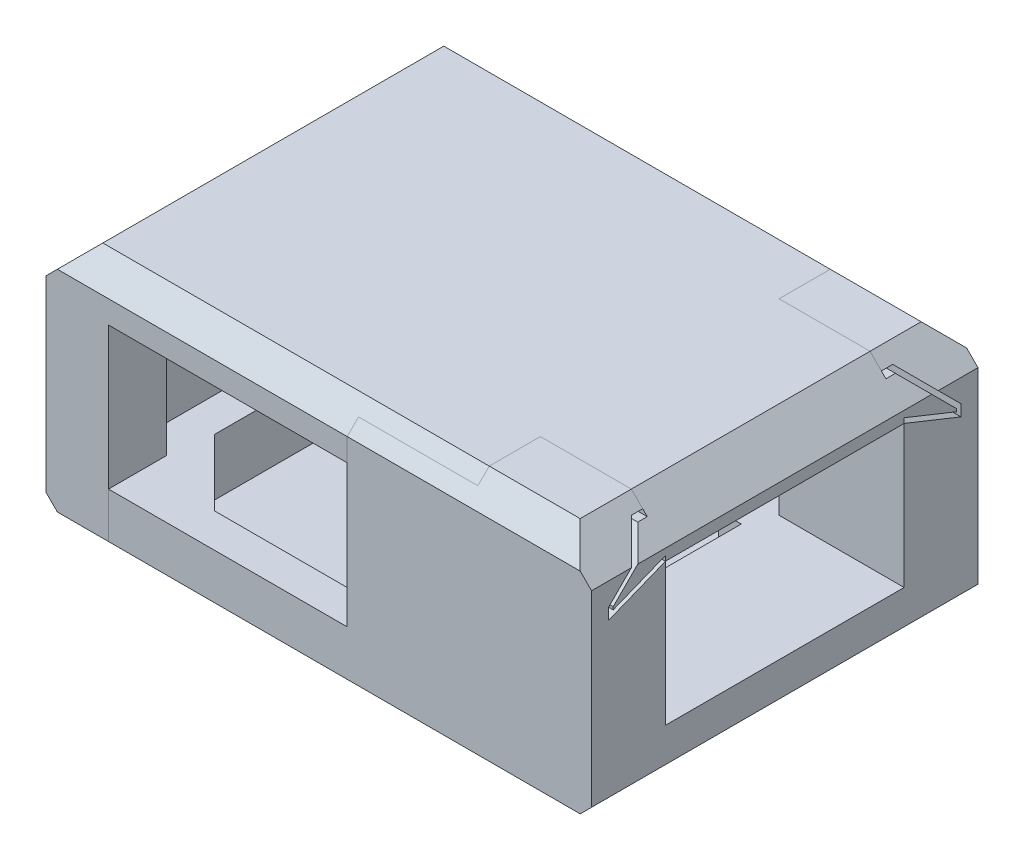
SolidWorks part; units mm, degrees
ref_plane "Front Plane" through (0, 0, 0) normal (0, 0, 1) x (1, 0, 0)
ref_plane "Top Plane" through (0, 0, 0) normal (0, 1, 0) x (1, 0, 0)
ref_plane "Right Plane" through (0, 0, 0) normal (1, 0, 0) x (0, 0, -1)
sketch "Sketch1" plane through (0, 0, 0) normal (0, 1, 0) x (1, 0, 0)
  line L0 (-4.5, 8) -> (-8, 4.5)
  line L1 (8, -8) -> (-4.5, -8)
  line L2 (8, -8) -> (8, 8)
  line L3 (8, 8) -> (-4.5, 8)
  line L4 (-8, -4.5) -> (-8, 4.5)
  line L5 (8, -8) -> (-8, 8) construction
  line L6 (8, 8) -> (-8, -8) construction
  line L7 (-4.5, -8) -> (-8, -4.5)
  point P0 (0, 0)
  dimension "D1" = 16
  dimension "D2" = 16
extrude "Boss-Extrude1" add sketch "Sketch1" along normal blind 1
sketch "Sketch2" plane through (0, 1, 0) normal (0, 1, 0) x (1, 0, 0)
  line L0 (8, -8) -> (8, 8) construction
  line L1 (3, 2) -> (-7, 2)
  line L2 (3, 2) -> (3, 8.5)
  line L3 (3, 8.5) -> (-7, 8.5)
  line L4 (-7, 2) -> (-7, 8.5)
  line L5 (7.5, 5) -> (14, 5)
  line L6 (7.5, 5) -> (7.5, 0)
  line L7 (7.5, 0) -> (14, 0)
  line L8 (14, 5) -> (14, 0)
  line L9 (8, 8) -> (-4.5, 8) construction
  line L10 (-8, 4.5) -> (-8, -4.5) construction
  point P11 (4.1326, 3.3307)
  dimension "D1" = 5
  dimension "D2" = 6.5
  dimension "D3" = 0.5
  dimension "D4" = 10
  dimension "D5" = 6.5
  dimension "D6" = 0.5
  dimension "D7" = 1
extrude "Boss-Extrude2" add sketch "Sketch2" along normal blind 5
mirror "Mirror2" about plane through (0, 0, 0) normal (0, 0, 1) of "Boss-Extrude2"
sketch "Sketch3" plane through (0, 0, 0) normal (0, -1, 0) x (1, 0, 0)
  line L0 (-8, 0) -> (8, 0) construction
  line L1 (-8, -4.5) -> (-8, 4.5) construction
  line L2 (8, 5) -> (8, -5) construction
  circle A0 centre (1, 2) radius 0.25
  circle A1 centre (-2, 2) radius 0.25
  circle A2 centre (-5, 2) radius 0.25
  circle A3 centre (-5, -2) radius 0.25
  circle A4 centre (-2, -2) radius 0.25
  circle A5 centre (1, -2) radius 0.25
  circle A6 centre (7.2, 3) radius 0.25
  circle A7 centre (7.2, 0) radius 0.25
  circle A8 centre (7.2, -3) radius 0.25
  point P25 (0, 0)
  point P26 (0, 0)
  point P27 (0, 0)
  point P28 (7.1653, 0)
  dimension "D4" = 0.5
  dimension "D8" = 0.5
  dimension "D1" = 2
  dimension "D2" = 3
  dimension "D3" = 3
  dimension "D5" = 3
  dimension "D6" = 3
  dimension "D7" = 3
  dimension "D9" = 0.8
extrude "Boss-Extrude3" add sketch "Sketch3" along normal blind 2
sketch "Sketch4" plane through (14, 0, 0) normal (1, 0, 0) x (0, 0, -1)
  line L4 (3.5, 1.5) -> (4.5, 2.5)
  line L5 (-4.5, 3.5) -> (4.5, 3.5) construction
  line L8 (-4.5, 1.5) -> (4.5, 1.5)
  line L9 (4.5, 1.5) -> (4.5, 5.5)
  line L10 (4.5, 5.5) -> (-4.5, 5.5)
  line L11 (-4.5, 5.5) -> (-4.5, 1.5)
  line L12 (-4.5, 1.5) -> (3.5, 1.5)
  line L13 (4.5, 2.5) -> (4.5, 5.5)
  line L14 (4.5, 5.5) -> (-4.5, 5.5)
  line L15 (-4.5, 5.5) -> (-4.5, 1.5)
  circle A0 centre (0, 3.5) radius 0.25
  circle A1 centre (-2.75, 3.5) radius 0.25
  circle A2 centre (2.75, 3.5) radius 0.25
  point P12 (0, 3.5)
  point P15 (-2.4617, 3.5)
  point P16 (2.7606, 3.5)
  dimension "D5" = 0.5
  dimension "D2" = 2.75
  dimension "D3" = 2.75
  dimension "D1" = 0.5
extrude "Cut-Extrude1" cut sketch "Sketch4" against normal blind 5
sketch "Sketch5" plane through (0, 0, 0) normal (0, -1, 0) x (1, 0, 0)
  line L0 (8, 8) -> (14, 8)
  line L1 (8, -8) -> (14, -8)
  line L4 (8.5, 8) -> (8.5, -8)
  line L5 (8.5, 8) -> (8.5, -8)
  line L6 (-10, 0) -> (14, 0) construction
  line L7 (7, 4.0858) -> (9, 4.0858)
  line L8 (7, 4.0858) -> (7, -4.0858)
  line L9 (7, -4.0858) -> (9, -4.0858)
  line L10 (9, 4.0858) -> (9, -4.0858)
  line L11 (-10, 8.5) -> (14, 8.5)
  line L12 (7, -7) -> (7, 7)
  line L13 (7, 7) -> (-4.0858, 7)
  line L14 (-4.0858, 7) -> (-7, 4.0858)
  line L15 (-7, 4.0858) -> (-7, -4.0858)
  line L16 (-7, -4.0858) -> (-4.0858, -7)
  line L17 (-4.0858, -7) -> (7, -7)
  line L18 (7, -7) -> (7, 7)
  line L19 (7, 7) -> (-4.0858, 7)
  line L20 (-4.0858, 7) -> (-7, 4.0858)
  line L21 (-7, 4.0858) -> (-7, -4.0858)
  line L22 (-7, -4.0858) -> (-4.0858, -7)
  line L23 (-4.0858, -7) -> (7, -7)
  line L24 (-10, 8.5) -> (-10, -8.5)
  line L25 (-10, -8.5) -> (14, -8.5)
  line L26 (14, 8.5) -> (14, -8.5)
  line L27 (2, 8.5) -> (2, -8.5) construction
  line L29 (14, 5.25) -> (8, 5.25)
  line L30 (14, 5.25) -> (8, 5.25)
  line L31 (3.25, 8.5) -> (3.25, 8)
  line L32 (14, -5.25) -> (8, -5.25)
  line L33 (14, -5.25) -> (8, -5.25)
  line L34 (-4.5, 8) -> (8, 8) construction
  line L35 (3, 8) -> (3, 8.5) construction
  line L38 (3.25, -8) -> (3.25, -8.5)
  line L39 (3.25, -8) -> (3.25, -8.5)
  line L54 (-7.25, 8.5) -> (-7.25, 5.5)
  line L55 (-7.25, 8.5) -> (-7.25, 5.9571)
  line L57 (-8.3536, 4.8536) -> (-4.8536, 8.3536)
  line L58 (-8.5, 4.7071) -> (-7.25, 5.9571)
  line L59 (-7.25, -8.5) -> (-7.25, -5.9571)
  line L60 (-8.5, -4.5) -> (-8.5, 4.5)
  line L61 (-8.5, -4.7071) -> (-8.5, 4.7071)
  line L62 (-8.5, -4.7071) -> (-7.25, -5.9571)
  point P32 (-8.5, 0)
  line M34 (8, -8) -> (8, 8)
  line M35 (8, 8) -> (-4.5, 8)
  line M36 (-4.5, 8) -> (-8, 4.5)
  line M37 (-8, 4.5) -> (-8, -4.5)
  line M38 (-8, -4.5) -> (-4.5, -8)
  line M39 (-4.5, -8) -> (8, -8)
  dimension "D2" = 2
  dimension "D3" = 17
  dimension "D4" = 24
  dimension "D5" = 2
  dimension "D12" = 0.25
  dimension "D1" = 1
  dimension "D6" = 0.25
  dimension "D7" = 0.5
  dimension "D8" = 0.5
  dimension "D9" = 0.5
  dimension "D10" = 0.25
  dimension "D11" = 0.25
  dimension "D13" = 0.25
extrude "Boss-Extrude5" add sketch "Sketch5" along normal blind 3 separate body contours L23 L22 L21 L20 L19 L18 L7 L9 M34 M35 M36 M37 M38 M39 | L5 L33 L1 M34 | L33 L5 L9 M34 | L10 L7 L5 L9 | L9 L5 L7 M34 | L33 L26 L30 L5 L7 L10 L9 | L26 L33 L5 L1 | L39 L25 L26 L1 M39 | L61 L62 L59 L25 L39 L31 L11 L55 L58 M39 M38 M37 M36 M35 | L62 L61 L58 L55 L11 L24 L25 L59 | L30 L26 L0 L5 | L30 L5 L0 M34 | L5 L30 L7 M34 | L11 L31 L0 L26 M35 region at (8.625, 0, 8.25) region at (8.25, 0, 6.625) region at (7.7737, 0, 6.625) region at (11.25, 0, 6.625) region at (8.25, 0, 4.6679) region at (-0.625, 0, 8.2067) region at (11.4403, 0, 0) region at (8.25, 0, 0) region at (8.75, 0, 0) region at (8.25, 0, -4.6679) region at (-8.9339, 0, 0) region at (11.25, 0, -6.625) region at (8.25, 0, -6.625) region at (8.625, 0, -8.25)
sketch "Sketch6" plane through (0, -3, 0) normal (0, -1, 0) x (1, 0, 0)
  line L0 (-7, 4.0858) -> (-7, -4.0858) construction
  line L1 (-7, -4.0858) -> (-4.0858, -7) construction
  line L2 (-4.0858, -7) -> (7, -7) construction
  line L3 (7, -7) -> (7, -4.0858) construction
  line L4 (7, -4.0858) -> (8, -4.0858) construction
  line L5 (8, -4.0858) -> (8, 4.0858) construction
  line L6 (7, 4.0858) -> (8, 4.0858) construction
  line L7 (7, 4.0858) -> (7, 7) construction
  line L8 (7, 7) -> (-4.0858, 7) construction
  line L9 (-4.0858, 7) -> (-7, 4.0858) construction
  line L10 (-7, 4.0858) -> (-7, -4.0858)
  line L11 (-7, -4.0858) -> (-4.0858, -7)
  line L12 (-4.0858, -7) -> (7, -7)
  line L13 (7, -7) -> (7, -4.0858)
  line L14 (7, -4.0858) -> (8, -4.0858)
  line L15 (8, -4.0858) -> (8, 4.0858)
  line L16 (7, 4.0858) -> (8, 4.0858)
  line L17 (7, 4.0858) -> (7, 7)
  line L18 (7, 7) -> (-4.0858, 7)
  line L19 (-4.0858, 7) -> (-7, 4.0858)
extrude "Boss-Extrude7" add sketch "Sketch6" against normal blind 0.5
ref_plane "Plane1" through (0, 6.25, 0) normal (0, 1, 0) x (1, 0, 0)
sketch "Sketch8" plane through (0, 6.25, 0) normal (0, 1, 0) x (1, 0, 0)
  line L4 (14, -8.5) -> (14, 8.5)
  line L5 (14, 8.5) -> (-10, 8.5)
  line L6 (-10, 8.5) -> (-10, -8.5)
  line L7 (-10, -8.5) -> (14, -8.5)
  line L8 (14, -8.5) -> (14, 8.5)
  line L9 (14, 8.5) -> (-10, 8.5)
  line L10 (-10, 8.5) -> (-10, -8.5)
  line L11 (-10, -8.5) -> (14, -8.5)
  dimension "D1" = 0
extrude "Boss-Extrude8" add sketch "Sketch8" along normal blind 2 separate body
extrude "Boss-Extrude11" add sketch "Sketch5<3>" against normal blind 6.25 separate body contours L30 L26 L0 L5 | L26 L33 L5 L1 | L62 L61 L58 L55 L11 L24 L25 L59 | L39 L25 L26 L1 M39 | L11 L31 L0 L26 M35 region at (8.625, 0, 8.25) region at (11.25, 0, 6.625) region at (-8.9339, 0, 0) region at (11.25, 0, -6.625) region at (8.625, 0, -8.25)
sketch "Sketch5<3>" plane through (0, 0, 0) normal (0, -1, 0) x (1, 0, 0) same geometry as "Sketch5"
combine bodies "Combine1" operation type add bodies to combine 109 112
combine bodies "Combine2" operation type add bodies to combine 108 110 111
extrude "Cut-Extrude2" cut sketch "Sketch5<4>" along normal blind 6.25 contours L62 L61 L58 L55 L11 L24 L25 L59 region at (-8.9339, 0, 0)
sketch "Sketch5<4>" plane through (0, 0, 0) normal (0, -1, 0) x (1, 0, 0) same geometry as "Sketch5"
extrude "Cut-Extrude3" cut sketch "Sketch5<5>" against normal blind 16.25 contours L26 L33 L5 L1 | L39 L25 L26 L1 M39 | L11 L31 L0 L26 M35 | L30 L26 L0 L5 region at (8.625, 0, 8.25) region at (11.25, 0, 6.625) region at (11.25, 0, -6.625) region at (8.625, 0, -8.25)
sketch "Sketch5<5>" plane through (0, 0, 0) normal (0, -1, 0) x (1, 0, 0) same geometry as "Sketch5"
extrude "Boss-Extrude12" add sketch "Sketch5<6>" along normal blind 3 contours L62 L61 L58 L55 L11 L24 L25 L59 region at (-8.9339, 0, 0)
sketch "Sketch5<6>" plane through (0, 0, 0) normal (0, -1, 0) x (1, 0, 0) same geometry as "Sketch5"
sketch "Sketch9" plane through (0, 6.25, 0) normal (0, 1, 0) x (1, 0, 0)
  line L6 (14, -5.25) -> (8.5, -5.25)
  line L7 (8.5, -5.25) -> (8.5, -8)
  line L8 (8.5, -8) -> (3.25, -8)
  line L9 (3.25, -8) -> (3.25, -8.5)
  line L10 (3.25, -8.5) -> (14, -8.5)
  line L11 (14, -8.5) -> (14, -5.25)
  line L12 (14, -5.25) -> (8.5, -5.25)
  line L13 (8.5, -5.25) -> (8.5, -8)
  line L14 (8.5, -8) -> (3.25, -8)
  line L15 (3.25, -8) -> (3.25, -8.5)
  line L16 (3.25, -8.5) -> (14, -8.5)
  line L17 (14, -8.5) -> (14, -5.25)
  line L18 (14, 5.25) -> (14, 8.5)
  line L19 (14, 8.5) -> (3.25, 8.5)
  line L20 (3.25, 8.5) -> (3.25, 8)
  line L21 (3.25, 8) -> (8.5, 8)
  line L22 (8.5, 8) -> (8.5, 5.25)
  line L23 (8.5, 5.25) -> (14, 5.25)
  line L24 (14, 5.25) -> (14, 8.5)
  line L25 (14, 8.5) -> (3.25, 8.5)
  line L26 (3.25, 8.5) -> (3.25, 8)
  line L27 (3.25, 8) -> (8.5, 8)
  line L28 (8.5, 8) -> (8.5, 5.25)
  line L29 (8.5, 5.25) -> (14, 5.25)
  dimension "D1" = 0
  dimension "D2" = 0
extrude "Boss-Extrude15" add sketch "Sketch9" along normal blind 2
chamfer "Chamfer1" distance 1 angle 45 2 edges at (3.375, -3, 8.5) (3.375, -3, -8.5)
chamfer "Chamfer2" distance 1 angle 45 2 edges at (8.625, 8.25, 8.5) (8.625, 8.25, -8.5)
chamfer "Chamfer3" distance 1 angle 45 4 edges at (-8.625, -3, 8.5) (-8.625, -3, -8.5) (-3.375, 8.25, 8.5) (-3.375, 8.25, -8.5)
sketch "Sketch10" plane through (14, 0, 0) normal (1, 0, 0) x (0, 0, -1)
  line L0 (-5.25, 7.75) -> (-5.75, 7.75)
  line L1 (-5.25, 8.25) -> (-5.25, 0) construction
  line L2 (-5.75, 7.75) -> (-7.75, 5.75)
  line L3 (-7.75, 5.75) -> (-7.75, 5.25)
  line L4 (-7.75, 5.25) -> (-5.25, 6.25)
  line L5 (-4.7071, 6.25) -> (-5.9571, 6.25) construction
  line L6 (-5.25, 7.75) -> (-5.25, 6.25)
  line L7 (0, 0) -> (0, 8.25) construction
  line L8 (-5.25, 8.25) -> (5.25, 8.25) construction
  line L9 (-5.6672, 7.55) -> (-7.55, 5.6672)
  line L10 (-7.55, 5.6672) -> (-7.55, 5.5454)
  line L11 (-7.55, 5.5454) -> (-5.45, 6.3854)
  line L14 (-5.45, 7.55) -> (-5.45, 6.3854) construction
  line L15 (-5.45, 7.55) -> (-5.6672, 7.55) construction
  line L16 (-5.6672, 7.55) -> (-5.25, 7.55)
  line L17 (-5.45, 6.3854) -> (-5.25, 6.4654)
  line L18 (5.45, 6.3854) -> (5.25, 6.4654)
  line L19 (5.6672, 7.55) -> (5.25, 7.55)
  line L20 (7.55, 5.5454) -> (5.45, 6.3854)
  line L21 (7.55, 5.6672) -> (7.55, 5.5454)
  line L22 (5.6672, 7.55) -> (7.55, 5.6672)
  line L23 (5.25, 7.75) -> (5.25, 6.25)
  line L24 (7.75, 5.25) -> (5.25, 6.25)
  line L25 (7.75, 5.75) -> (7.75, 5.25)
  line L26 (5.75, 7.75) -> (7.75, 5.75)
  line L27 (5.25, 7.75) -> (5.75, 7.75)
  point P21 (-5.45, 6.3854)
  line M21 (5.25, 8.25) -> (5.25, 0)
  line M23 (-5.25, 0) -> (-5.25, 8.25)
  dimension "D1" = 1
  dimension "D2" = 0.5
  dimension "D3" = 2.5
  dimension "D4" = 0.5
  dimension "D5" = 1.5
  dimension "D6" = 0.2
extrude "Cut-Extrude4" cut sketch "Sketch10" against normal blind 12 contours L17 L11 L10 L9 L16 L6 L0 L2 L3 L4 M23 | L11 L17 L6 L16 L9 L10 | L22 L19 L18 L20 L21 M21 | L27 L19 L22 L21 L20 L18 L24 L25 L26 M21 region at (14, 7.65, 5.2854) region at (14, 6.5881, 6.1077) region at (14, 5.9326, -6.4869) region at (14, 6.5881, -6.1077)
extrude "Boss-Extrude17" add sketch "Sketch10<4>" against normal blind 5.5 contours L22 L19 L18 L20 L21 M21 | L11 L17 L6 L16 L9 L10 region at (14, 6.5881, 6.1077) region at (14, 6.5881, -6.1077)
sketch "Sketch10<4>" plane through (14, 0, 0) normal (1, 0, 0) x (0, 0, -1) same geometry as "Sketch10"
chamfer "Chamfer4" distance 1.5 angle 45 3 edges at (14, 8.25, -6.375) (14, 8.25, 6.375) (14, -3, 0)
chamfer "Chamfer5" distance 1.5 angle 45 3 edges at (14, 8.25, 0) (-10, -3, 0) (-10, 8.25, 0)
sketch "Sketch11" plane through (0, 0, -8.5) normal (0, 0, -1) x (-1, 0, 0)
  line L0 (5.5, 1.5) -> (6.5, 2.5)
  line L1 (-2.5, 3.5) -> (6.5, 3.5) construction
  line L2 (-2.5, 1.5) -> (5.5, 1.5)
  line L3 (6.5, 2.5) -> (6.5, 5.5)
  line L4 (6.5, 5.5) -> (-2.5, 5.5)
  line L5 (-2.5, 5.5) -> (-2.5, 1.5)
  line L6 (2, 6) -> (2, 1) construction
  line L7 (-3, 6) -> (7, 6) construction
  line L8 (-3, 1) -> (7, 1) construction
  circle A0 centre (2, 3.5) radius 0.25
  circle A1 centre (-0.75, 3.5) radius 0.25
  circle A2 centre (4.75, 3.5) radius 0.25
  point P13 (0, 0)
  point P14 (-2.3205, 5.5)
  dimension "D3" = 0.5
  dimension "D1" = 2.75
  dimension "D2" = 2.75
  dimension "D4" = 4
  dimension "D5" = 9
  dimension "D6" = 135
  dimension "D7" = 1
  dimension "D8" = 1
extrude "Cut-Extrude5" cut sketch "Sketch11" against normal blind 4
mirror "Mirror3" about plane through (0, 0, 0) normal (0, 0, 1) of "Cut-Extrude5"
delete or keep bodies "Body-Delete/Keep 1" type delete bodies bodies 122
